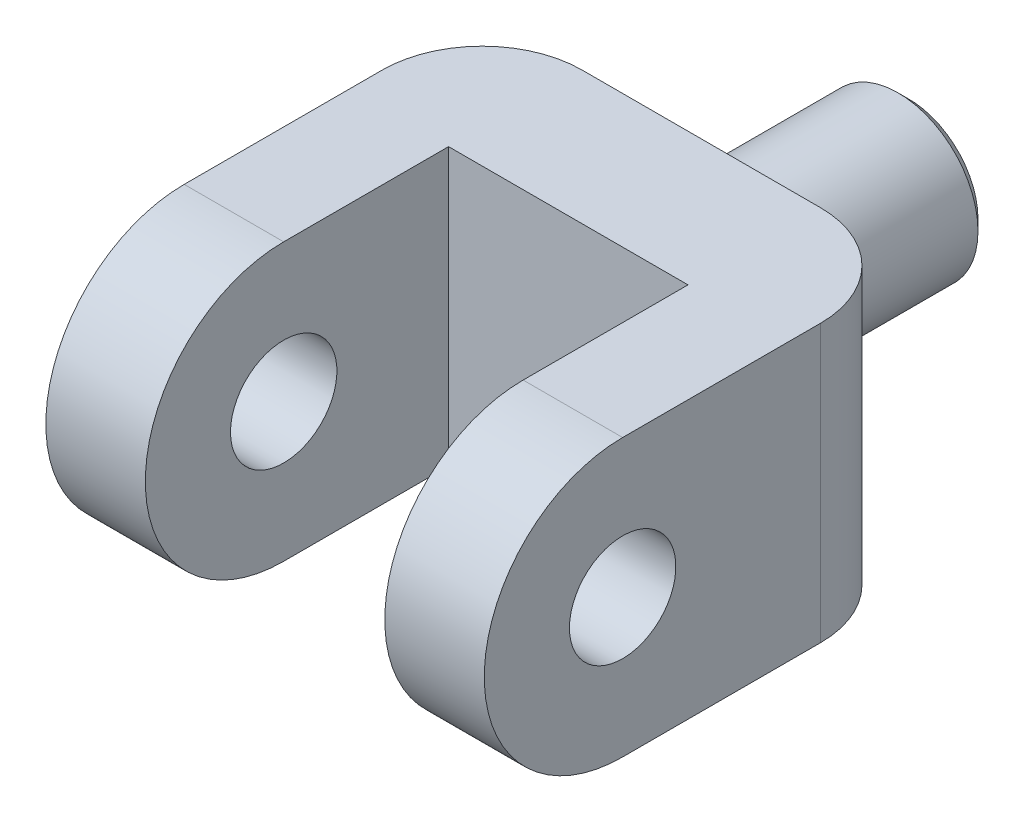
SolidWorks part; units mm, degrees
ref_plane "Alzado" through (0, 0, 0) normal (0, 0, 1) x (1, 0, 0)
ref_plane "Planta" through (0, 0, 0) normal (0, 1, 0) x (1, 0, 0)
ref_plane "Vista lateral" through (0, 0, 0) normal (1, 0, 0) x (0, 0, -1)
sketch "Croquis1" plane through (0, 0, 0) normal (0, 1, 0) x (1, 0, 0)
  line L0 (-2.2236, 3.1695) -> (1.8964, 3.1695)
  line L1 (1.8964, 3.1695) -> (1.8964, -0.9305)
  line L2 (1.8964, -0.9305) -> (0.9614, -0.9305)
  line L3 (0.9614, -0.9305) -> (0.9614, 1.9188)
  line L4 (0.9614, 1.9188) -> (-1.2886, 1.9188)
  line L5 (-1.2886, 1.9188) -> (-1.2886, -0.9305)
  line L6 (-1.2886, -0.9305) -> (-2.2236, -0.9305)
  line L7 (-2.2236, -0.9305) -> (-2.2236, 3.1695)
  point P6 (-0.1636, 1.9188)
  point P9 (-0.1636, 3.1695)
  point P10 (0, 0)
  dimension "D1" = 4.12
  dimension "D2" = 4.1
  dimension "D3" = 4.1
  dimension "D4" = 2.25
  dimension "D5" = 0.935
  dimension "D6" = 0.935
extrude "Saliente-Extruir2" add sketch "Croquis1" along normal blind 2.6
fillet "Redondeo1" 2 edges at (1.4289, 2.6, 0.9305) (1.4289, 0, 0.9305) type full round first side face at (-0.1636, 2.6, -0.8068) second side face at (-0.1636, 0, -0.8068) middle face at (1.4289, 1.3, 0.9305)
fillet "Redondeo2" 2 edges at (-1.7561, 0, 0.9305) (-1.7561, 2.6, 0.9305) type full round first side face at (-0.1636, 0, -1.1318) second side face at (-0.1636, 2.6, -1.1318) middle face at (-1.7561, 1.3, 0.9305)
sketch "Croquis2" plane through (-2.2236, 0, 0) normal (-1, 0, 0) x (0, 0, 1)
  line L0 (-3.1695, 2.6) -> (-3.1695, 0) construction
  circle A0 centre (-0.3695, 1.3) radius 0.5
  arc A1 (-0.3695, 0) -> (-0.3695, 2.6) centre (-0.3695, 1.3) ccw construction
  point P5 (0.9305, 1.3)
  point P8 (-3.1695, 1.3)
  dimension "D1" = 1
  dimension "D2" = 1.3
extrude "Cortar-Extruir1" cut sketch "Croquis2" against normal through all
fillet "Redondeo4" radius 0.94 2 edges at (1.8964, 1.3, -3.1695) (-2.2236, 1.3, -3.1695)
sketch "Croquis3" plane through (0, 0, -1.9188) normal (0, 0, 1) x (1, 0, 0)
  line L0 (-1.2886, 2.6) -> (0.9614, 2.6) construction
  circle A1 centre (-0.1636, 1.3) radius 0.75
  point P2 (0, 0)
  point P5 (-0.1636, 2.6)
  dimension "D1" = 1.5
  dimension "D2" = 1.3
extrude "Saliente-Extruir3" add sketch "Croquis3" against normal blind 3.2
chamfer "Chaflán1" distance 0.1 angle 45 1 edges at (0.5864, 1.3, -5.1188)
